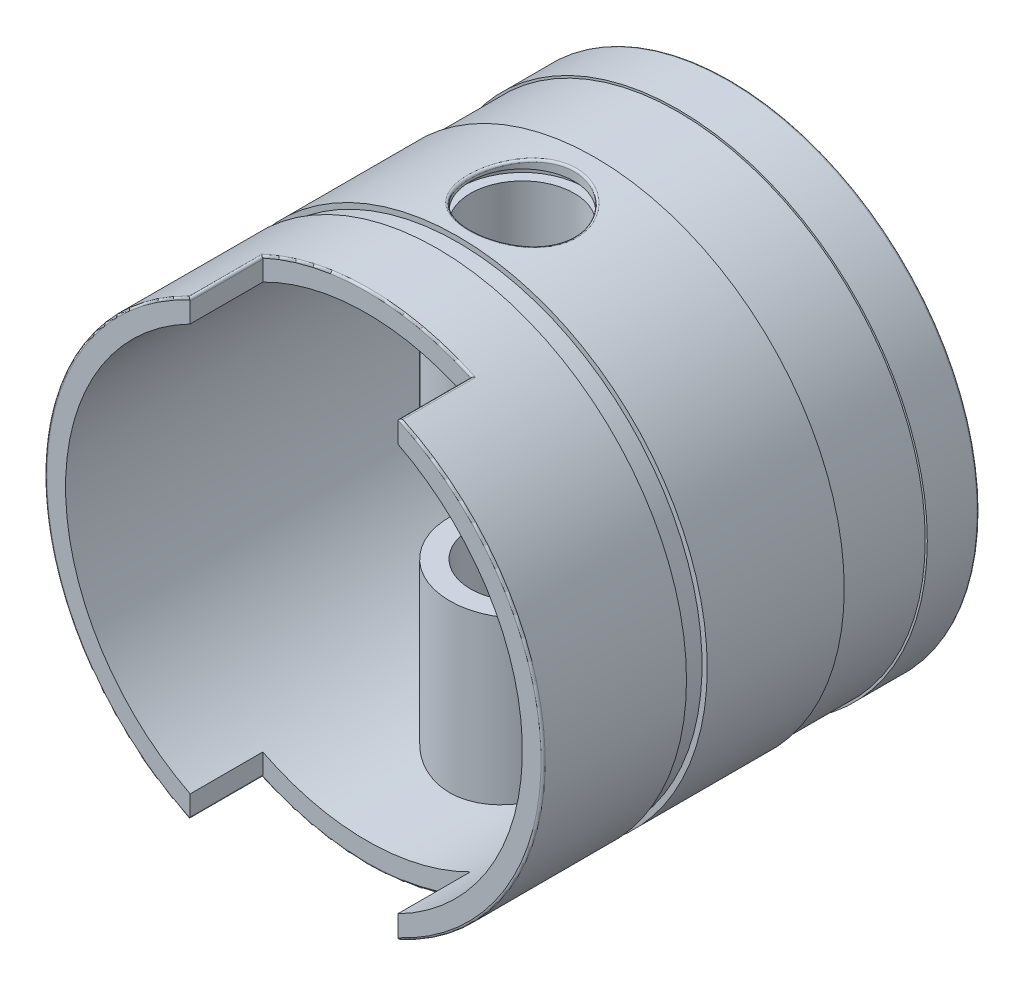
SolidWorks part; units mm, degrees
ref_plane "Front" through (0, 0, 0) normal (0, 0, 1) x (1, 0, 0)
ref_plane "Top" through (0, 0, 0) normal (0, 1, 0) x (1, 0, 0)
ref_plane "Right" through (0, 0, 0) normal (1, 0, 0) x (0, 0, -1)
sketch "Sketch1" plane through (0, 0, 0) normal (0, 0, 1) x (1, 0, 0)
  circle A0 centre (0, 0) radius 6
  dimension "D1" = 12
extrude "Boss-Extrude1" add sketch "Sketch1" along normal blind 0.5
sketch "Sketch2" plane through (0, 0, 0.5) normal (0, 0, 1) x (1, 0, 0)
  circle A0 centre (0, 0) radius 6 construction
  circle A1 centre (0, 0) radius 6
  circle A2 centre (0, 0) radius 5.5
  dimension "D1" = 0.5
extrude "Boss-Extrude2" add sketch "Sketch2" along normal blind 10
sketch "Sketch3" plane through (0, 0, 0) normal (0, 1, 0) x (1, 0, 0)
  circle A0 centre (0, -5) radius 1.25
  dimension "D1" = 2.5
  dimension "D2" = 5
extrude "Cut-Extrude1" cut sketch "Sketch3" against normal blind 12 and the other way blind 12
sketch "Sketch4" plane through (0, 0, 0) normal (0, 1, 0) x (1, 0, 0)
  circle A0 centre (0, -5) radius 1.25 construction
  circle A1 centre (0, -5) radius 1.25
  circle A2 centre (0, -5) radius 1.75
  dimension "D1" = 0.5
extrude "Boss-Extrude3" add sketch "Sketch4" along normal up to surface (5.5 mm away) up to face at (-0.2518, -5.4942, 6.2244)
sketch "Sketch5" plane through (0, 0, 0) normal (0, -1, 0) x (1, 0, 0)
  circle A0 centre (0, 5) radius 1.75 construction
  circle A1 centre (0, 5) radius 1.25 construction
  circle A2 centre (0, 5) radius 1.75
  circle A3 centre (0, 5) radius 1.25
extrude "Cut-Extrude2" cut sketch "Sketch5" against normal blind 1
mirror "Mirror2" about plane through (0, 0, 0) normal (0, 1, 0) of "Cut-Extrude2", "Boss-Extrude3"
sketch "Sketch6" plane through (0, 0, 0) normal (0, 1, 0) x (1, 0, 0)
  line L0 (0, 0) -> (0, -31.5114) construction
  line L1 (-6, -10.5) -> (6, -10.5) construction
  line L2 (2.5, -8.75) -> (-2.5, -8.75)
  line L3 (2.5, -8.75) -> (2.5, -13.3173)
  line L4 (2.5, -13.3173) -> (-2.5, -13.3173)
  line L5 (-2.5, -8.75) -> (-2.5, -13.3173)
  point P7 (0, -13.3173)
  dimension "D1" = 5
  dimension "D2" = 1.75
extrude "Cut-Extrude3" cut sketch "Sketch6" against normal blind 8 and the other way blind 8
ref_plane "Plane1" through (0, -5.5, 0) normal (0, 1, 0) x (1, 0, 0)
sketch "Sketch7" plane through (0, -5.5, 0) normal (0, 1, 0) x (1, 0, 0)
  circle A0 centre (0, -5) radius 1.25 construction
  circle A1 centre (0, -5) radius 1.25
  circle A2 centre (0, -5) radius 1.5
  dimension "D1" = 0.25
ref_plane "Plane2" through (0, -5.75, 0) normal (0, 1, 0) x (1, 0, 0)
extrude "Cut-Extrude4" cut sketch "Sketch7" against normal blind 0.25
mirror "Mirror3" about plane through (0, 0, 0) normal (0, 1, 0) of "Cut-Extrude4"
fillet "Fillet1" radius 0.05 11 edges at (6, 0, 10.5) (2.5, 5.4544, 9.625) (0, 6, 8.75) (-2.5, 5.4544, 9.625) (-6, 0, 10.5) (-2.5, -5.4544, 9.625) (0, -6, 8.75) (2.5, -5.4544, 9.625) (-0.2574, -5.9945, 6.2232) (0.2574, 5.9945, 6.2232) (6, 0, 0)
ref_plane "Plane3" through (0, 0, 0) normal (0, 0, -1) x (-1, 0, 0)
ref_plane "Plane4" through (0, 0, 1.25) normal (0, 0, -1) x (-1, 0, 0)
sketch "Sketch10" plane through (0, 0, 1.25) normal (0, 0, -1) x (-1, 0, 0)
  circle A0 centre (0, 0) radius 6 construction
  circle A1 centre (0, 0) radius 6
  circle A2 centre (0, 0) radius 5.95
  dimension "D1" = 0.05
extrude "Cut-Extrude6" cut sketch "Sketch10" against normal blind 2
sketch "Sketch11" plane through (0, 0, 3.25) normal (0, 0, -1) x (-1, 0, 0)
  circle A1 centre (0, 0) radius 6
  circle A2 centre (0, 0) radius 6
  dimension "D1" = 0
ref_plane "Plane5" through (0, 0, 6.5485) normal (0, 0, -1) x (-1, 0, 0)
sketch "Sketch12" plane through (0, 0, 6.5485) normal (0, 0, -1) x (-1, 0, 0)
  circle A0 centre (0, 0) radius 5.875
  circle A1 centre (0, 0) radius 6
  circle A2 centre (0, 0) radius 6
  dimension "D1" = 0
  dimension "D2" = 0.125
extrude "Cut-Extrude7" cut sketch "Sketch12" against normal blind 0.5
sketch "Sketch20" plane through (0, 0, 0) normal (0, 0, 1) x (1, 0, 0)
  line L0 (-2.7447, 1.5) -> (-2.7447, -1.5)
  line L1 (-2.7447, 1.5) -> (3.1332, 1.5)
  line L7 (-2.7447, -1.5) -> (3.1332, -1.5)
  line L9 (3.1332, 1.5) -> (3.1332, -1.5)
ref_plane "Plane6" through (0, 0, 0) normal (0, 0, 1) x (1, 0, 0)
sketch "Sketch22" plane through (0, -1, 0) normal (0, 1, 0) x (1, 0, 0)
  circle A0 centre (0, -5) radius 1.25 construction
  circle A1 centre (0, -5) radius 1.25
ref_plane "Plane7" through (0, 0, 5) normal (0, 0, 1) x (1, 0, 0)
sketch "Sketch23" plane through (0, 0, 5) normal (0, 0, 1) x (1, 0, 0)
  line L4 (-2.7447, 1.5) -> (-2.7447, -1.5)
  line L5 (-2.7447, -1.5) -> (3.1332, -1.5)
  line L6 (3.1332, -1.5) -> (3.1332, 1.5)
  line L7 (3.1332, 1.5) -> (-2.7447, 1.5)
  line L8 (-2.7447, 1.5) -> (-2.7447, -1.5)
  line L9 (-2.7447, -1.5) -> (3.1332, -1.5)
  line L10 (3.1332, -1.5) -> (3.1332, 1.5)
  line L11 (3.1332, 1.5) -> (-2.7447, 1.5)
  dimension "D1" = 0
extrude "Cut-Extrude8" cut sketch "Sketch23" against normal blind 2 and the other way blind 2
